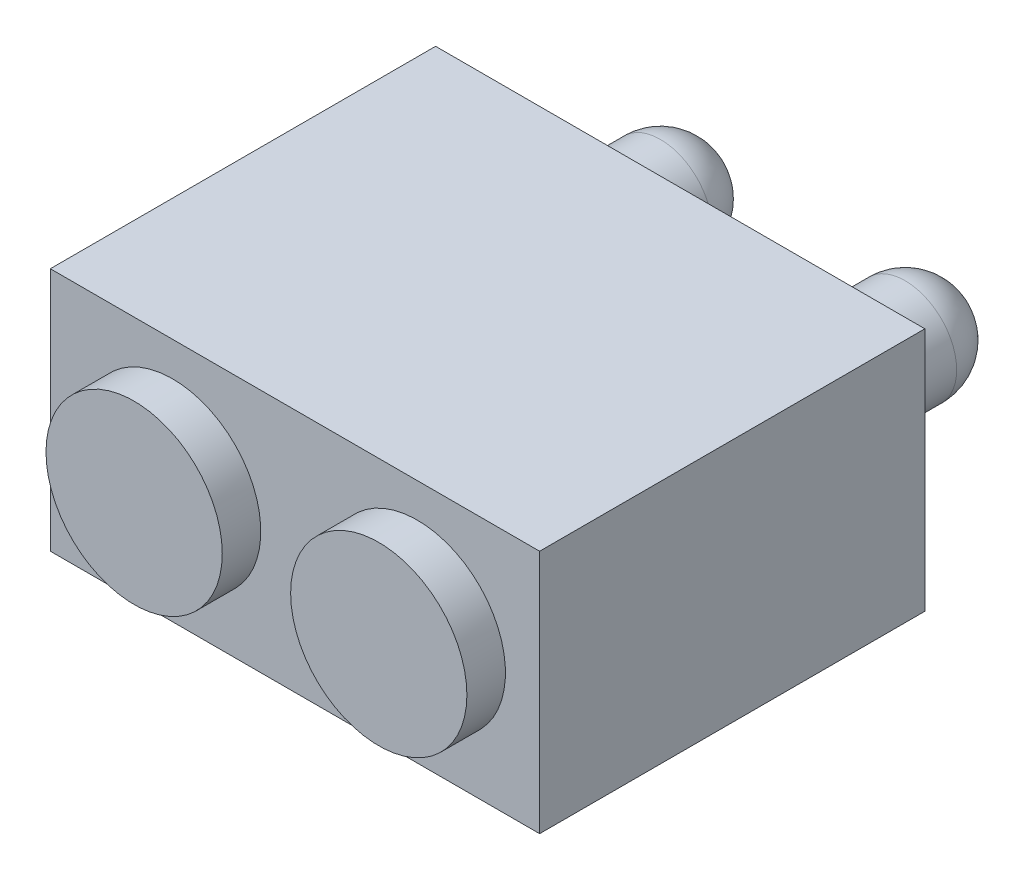
SolidWorks part; units mm, degrees
material "ABS"
ref_plane "Plan de face" through (0, 0, 0) normal (0, 0, 1) x (1, 0, 0)
ref_plane "Plan de dessus" through (0, 0, 0) normal (0, 1, 0) x (1, 0, 0)
ref_plane "Plan de droite" through (0, 0, 0) normal (1, 0, 0) x (0, 0, -1)
sketch "Esquisse1" plane through (0, 0, 0) normal (0, 0, 1) x (1, 0, 0)
  line L1 (0, 0) -> (5.08, 0)
  line L2 (0, 0) -> (0, 2.54)
  line L3 (0, 2.54) -> (5.08, 2.54)
  line L4 (5.08, 0) -> (5.08, 2.54)
  dimension "D1" = 2.54
  dimension "D2" = 5.08
extrude "Extrusion1" add sketch "Esquisse1" along normal blind 4
sketch "Esquisse2" plane through (0, 0, 4) normal (0, 0, 1) x (1, 0, 0)
  line L0 (2.54, 2.9529) -> (2.54, -0.4913) construction
  line L1 (1.27, 2.9529) -> (1.27, -0.4913) construction
  line L2 (3.81, 2.9529) -> (3.81, -0.4913) construction
  line L8 (5.08, 1.27) -> (0, 1.27) construction
  circle A0 centre (3.81, 1.27) radius 0.915
  circle A1 centre (1.27, 1.27) radius 0.915
  dimension "D1" = 1.27
  dimension "D2" = 1.27
extrude "Extrusion2" add sketch "Esquisse2" along normal blind 0.4
sketch "Esquisse3" plane through (0, 0, 0) normal (0, 0, -1) x (-1, 0, 0)
  circle A0 centre (-3.81, 1.27) radius 0.535
  circle A1 centre (-1.27, 1.27) radius 0.535
extrude "Extrusion3" add sketch "Esquisse3" along normal blind 1.065
dome "Dôme1" faces to dome 1 distance 0.535 reverse direction no elliptical dome no face at (3.275, 1.27, -1.065) parameters "D1"=0.535
dome "Dôme2" faces to dome 1 distance 0.535 reverse direction no elliptical dome no face at (0.735, 1.27, -1.065) parameters "D1"=0.535
